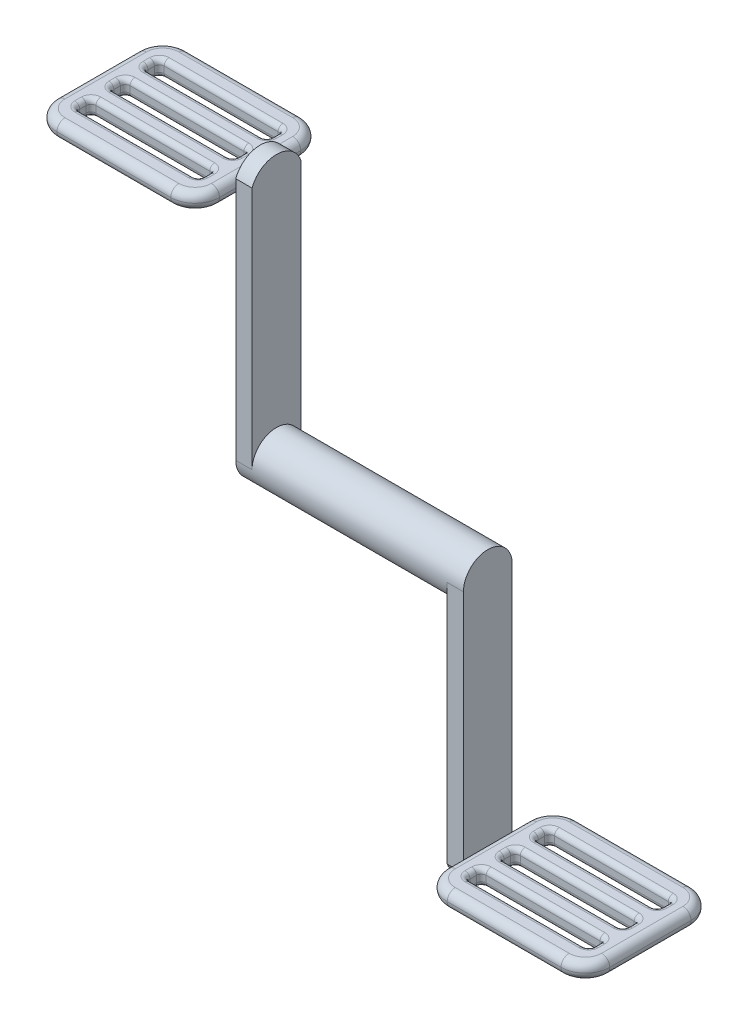
SolidWorks part; units mm, degrees
ref_plane "Front Plane" through (0, 0, 0) normal (0, 0, 1) x (1, 0, 0)
ref_plane "Top Plane" through (0, 0, 0) normal (0, 1, 0) x (1, 0, 0)
ref_plane "Right Plane" through (0, 0, 0) normal (1, 0, 0) x (0, 0, -1)
sketch "Sketch1" plane through (0, 0, 0) normal (1, 0, 0) x (0, 0, -1)
  circle A0 centre (0, 0) radius 15
  dimension "D1" = 30
extrude "Boss-Extrude1" add sketch "Sketch1" along normal blind 70 and the other way blind 70
sketch "Sketch2" plane through (-70, 0, 0) normal (-1, 0, 0) x (0, 0, 1)
  line L1 (15, 0) -> (-15, 0)
  line L2 (15, 0) -> (15, 150)
  line L4 (-15, 0) -> (-15, 150)
  circle A0 centre (0, 0) radius 15 construction
  arc A2 (-15, 150) -> (15, 150) centre (0, 144.4322) cw
  dimension "D2" = 16
  dimension "D1" = 150
  dimension "D3" = 150
extrude "Boss-Extrude2" add sketch "Sketch2" against normal blind 10
sketch "Sketch3" plane through (-70, 0, 0) normal (-1, 0, 0) x (0, 0, 1)
  line L1 (-40, 150) -> (40, 150)
  line L2 (-40, 150) -> (-40, 140)
  line L3 (-40, 140) -> (40, 140)
  line L4 (40, 150) -> (40, 140)
  point P6 (0, 150)
  dimension "D1" = 80
  dimension "D2" = 10
extrude "Boss-Extrude3" add sketch "Sketch3" along normal blind 100 separate body
sketch "Sketch4" plane through (70, 0, 0) normal (1, 0, 0) x (0, 0, -1)
  line L1 (-15, 0) -> (15, 0)
  line L2 (-15, 0) -> (-15, -150)
  line L4 (15, 0) -> (15, -150)
  circle A0 centre (0, 0) radius 15 construction
  arc A1 (-15, -150) -> (15, -150) centre (0, -144.4322) ccw
  dimension "D2" = 16
  dimension "D1" = 150
  dimension "D3" = 150
extrude "Boss-Extrude4" add sketch "Sketch4" against normal blind 10
sketch "Sketch5" plane through (70, 0, 0) normal (1, 0, 0) x (0, 0, -1)
  line L1 (40, -150) -> (-40, -150)
  line L2 (40, -150) -> (40, -140)
  line L3 (40, -140) -> (-40, -140)
  line L4 (-40, -150) -> (-40, -140)
  point P4 (0, -150)
  dimension "D1" = 80
  dimension "D2" = 10
extrude "Boss-Extrude5" add sketch "Sketch5" along normal blind 100
ref_axis "Axis1" through (-70, 0, 0) along (1, 0, 0)
fillet "Fillet1" radius 15 4 edges at (-70, 145, -40) (-70, 145, 40) (-170, 145, -40) (-170, 145, 40)
fillet "Fillet2" radius 5 16 edges at (-70, 140, 0) (-70, 150, 0) (-74.3934, 140, 35.6066) (-120, 140, 40) (-165.6066, 140, 35.6066) (-170, 140, 0) (-165.6066, 140, -35.6066) (-120, 140, -40) (-74.3934, 140, -35.6066) (-120, 150, 40) (-170, 150, 0) (-120, 150, -40) (-74.3934, 150, -35.6066) (-165.6066, 150, -35.6066) (-165.6066, 150, 35.6066) (-74.3934, 150, 35.6066)
sketch "Sketch7" plane through (0, 150, 0) normal (0, 1, 0) x (1, 0, 0)
  line L1 (-158, 26) -> (-82, 26)
  line L2 (-158, 26) -> (-158, 16)
  line L3 (-158, 16) -> (-82, 16)
  line L4 (-82, 26) -> (-82, 16)
  line L5 (-158, 5) -> (-82, 5)
  line L6 (-158, 5) -> (-158, -5)
  line L7 (-158, -5) -> (-82, -5)
  line L8 (-82, 5) -> (-82, -5)
  line L9 (-158, -16) -> (-82, -16)
  line L10 (-158, -16) -> (-158, -26)
  line L11 (-158, -26) -> (-82, -26)
  line L12 (-82, -16) -> (-82, -26)
  line L13 (-70, -25) -> (-70, 25) construction
  line L15 (-70, 25) -> (-70, -25) construction
  line L17 (-170, -25) -> (-170, 25) construction
  line L18 (-155, 40) -> (-85, 40) construction
  line L20 (-85, -40) -> (-155, -40) construction
  point P16 (-82, 0)
  dimension "D2" = 12
  dimension "D3" = 10
  dimension "D4" = 12
  dimension "D5" = 10
  dimension "D6" = 12
  dimension "D7" = 14
  dimension "D8" = 12
  dimension "D9" = 12
  dimension "D10" = 14
  dimension "D11" = 10
  dimension "D12" = 12
extrude "Cut-Extrude1" cut sketch "Sketch7" against normal through all
fillet "Fillet3" radius 3 36 edges at (-82, 140, -21) (-158, 140, -21) (-158, 145, -16) (-120, 140, -16) (-82, 145, -16) (-82, 145, -26) (-120, 140, -26) (-158, 145, -26) (-158, 140, 21) (-82, 140, 21) (-82, 140, 0) (-158, 140, 0) (-82, 145, 16) (-120, 140, 16) (-158, 145, 16) (-158, 145, 26) (-120, 140, 26) (-82, 145, 26) (-158, 145, 5) (-120, 140, 5) (-82, 145, 5) (-82, 145, -5) (-120, 140, -5) (-158, 145, -5) (-82, 150, 21) (-158, 150, 21) (-158, 150, 0) (-82, 150, 0) (-158, 150, -21) (-82, 150, -21) (-120, 150, 16) (-120, 150, 26) (-120, 150, 5) (-120, 150, -5) (-120, 150, -16) (-120, 150, -26)
fillet "Fillet4" radius 15 4 edges at (70, -145, -40) (170, -145, -40) (170, -145, 40) (70, -145, 40)
fillet "Fillet5" radius 5 16 edges at (165.6066, -140, -35.6066) (120, -140, -40) (74.3934, -140, -35.6066) (70, -140, 0) (74.3934, -140, 35.6066) (120, -140, 40) (165.6066, -140, 35.6066) (74.3934, -150, 35.6066) (120, -150, 40) (165.6066, -150, 35.6066) (170, -150, 0) (165.6066, -150, -35.6066) (120, -150, -40) (74.3934, -150, -35.6066) (70, -150, 0) (170, -140, 0)
sketch "Sketch8" plane through (0, -140, 0) normal (0, 1, 0) x (1, 0, 0)
  line L0 (70, 25) -> (70, -25) construction
  line L1 (82, 5) -> (158, 5)
  line L2 (82, 5) -> (82, -5)
  line L3 (82, -5) -> (158, -5)
  line L4 (158, 5) -> (158, -5)
  line L5 (170, -25) -> (170, 25) construction
  line L6 (155, 40) -> (85, 40) construction
  line L7 (82, 26) -> (158, 26)
  line L8 (82, 26) -> (82, 16)
  line L9 (82, 16) -> (158, 16)
  line L10 (158, 26) -> (158, 16)
  line L11 (85, -40) -> (155, -40) construction
  line L12 (82, -16) -> (158, -16)
  line L13 (82, -16) -> (82, -26)
  line L14 (82, -26) -> (158, -26)
  line L15 (158, -16) -> (158, -26)
  point P4 (82, 0)
  dimension "D1" = 12
  dimension "D2" = 12
  dimension "D3" = 10
  dimension "D4" = 14
  dimension "D5" = 12
  dimension "D6" = 12
  dimension "D7" = 10
  dimension "D8" = 10
  dimension "D9" = 12
  dimension "D10" = 12
  dimension "D11" = 14
extrude "Cut-Extrude2" cut sketch "Sketch8" against normal through all
fillet "Fillet6" radius 3 36 edges at (82, -150, 21) (158, -150, 21) (158, -140, 21) (82, -140, 21) (82, -150, 0) (158, -150, 0) (158, -140, 0) (82, -140, 0) (82, -150, -21) (158, -150, -21) (158, -140, -21) (82, -140, -21) (120, -150, -26) (82, -145, -26) (120, -140, -26) (158, -145, -26) (120, -150, 16) (82, -145, 16) (120, -140, 16) (158, -145, 16) (120, -150, 26) (158, -145, 26) (120, -140, 26) (82, -145, 26) (120, -150, -5) (82, -145, -5) (120, -140, -5) (158, -145, -5) (120, -150, 5) (158, -145, 5) (120, -140, 5) (82, -145, 5) (120, -150, -16) (158, -145, -16) (120, -140, -16) (82, -145, -16)
